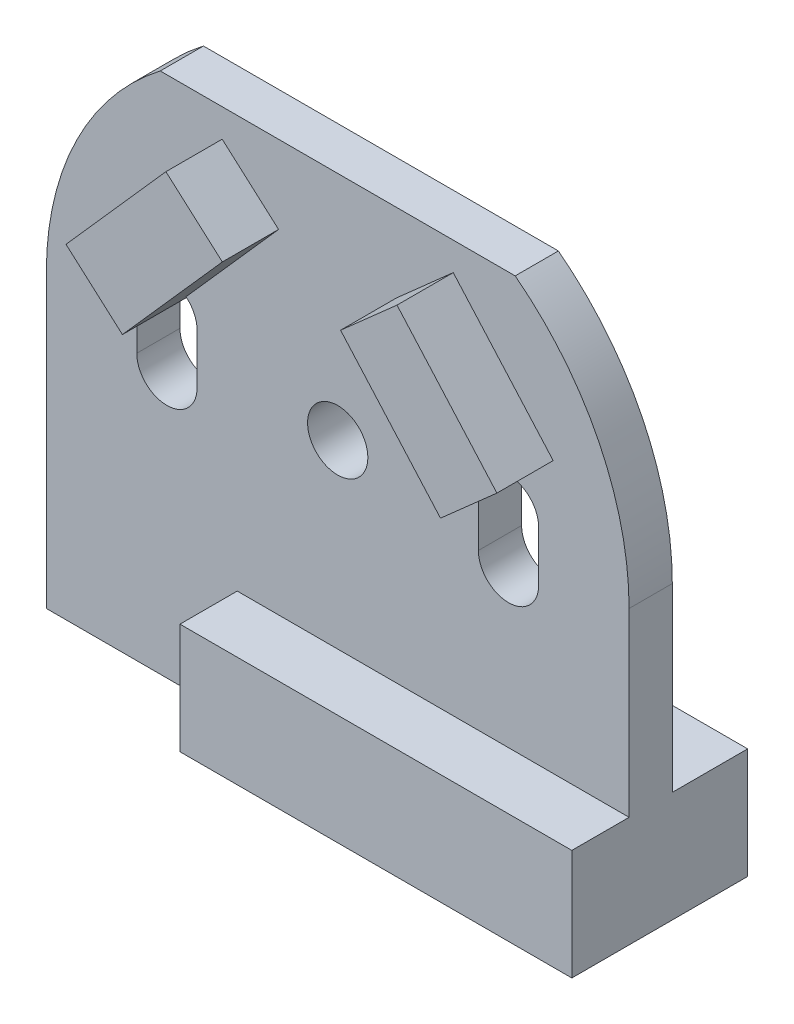
SolidWorks part; units mm, degrees
ref_plane "Front Plane" through (0, 0, 0) normal (0, 0, 1) x (1, 0, 0)
ref_plane "Top Plane" through (0, 0, 0) normal (0, 1, 0) x (1, 0, 0)
ref_plane "Right Plane" through (0, 0, 0) normal (1, 0, 0) x (0, 0, -1)
sketch "Sketch1" plane through (0, 0, 0) normal (0, 0, 1) x (1, 0, 0)
  line L0 (-3.4, 0.5) -> (-3.4, -0.5) construction
  line L1 (-5.8, -5.8) -> (5.8, -5.8)
  line L2 (-5.8, -5.8) -> (-5.8, 4.6)
  line L3 (-5.8, 4.6) -> (5.8, 4.6)
  line L4 (5.8, -5.8) -> (5.8, 4.6)
  line L5 (-2.8, 0.5) -> (-2.8, -0.5)
  line L6 (-4, 0.5) -> (-4, -0.5)
  line L7 (3.4, 0.5) -> (3.4, -0.5) construction
  line L8 (4, 0.5) -> (4, -0.5)
  line L9 (2.8, 0.5) -> (2.8, -0.5)
  line L10 (-2.3, 4.0398) -> (-4.2887, 1.7937)
  line L11 (-4.2887, 1.7937) -> (-3.1656, 0.7993)
  line L12 (-3.1656, 0.7993) -> (-1.1769, 3.0455)
  line L13 (-1.1769, 3.0455) -> (-2.3, 4.0398)
  line L14 (1.1769, 3.0455) -> (2.3, 4.0398)
  line L15 (2.3, 4.0398) -> (4.2887, 1.7937)
  line L16 (4.2887, 1.7937) -> (3.1656, 0.7993)
  line L17 (3.1656, 0.7993) -> (1.1769, 3.0455)
  line L18 (0, 0) -> (-2.1713, 1.9224) construction
  line L19 (0, 0) -> (2.1713, 1.9224) construction
  line L20 (0, 0) -> (0, 5.8) construction
  line L22 (5.8, -5.8) -> (-2, -5.8)
  line L23 (5.8, -5.8) -> (5.8, -3.6)
  line L24 (5.8, -3.6) -> (-2, -3.6)
  line L25 (-2, -5.8) -> (-2, -3.6)
  circle A0 centre (0, 0) radius 5.8
  circle A1 centre (0, 0) radius 0.6
  arc A2 (-2.8, 0.5) -> (-4, 0.5) centre (-3.4, 0.5) ccw
  arc A3 (-4, -0.5) -> (-2.8, -0.5) centre (-3.4, -0.5) ccw
  arc A4 (4, 0.5) -> (2.8, 0.5) centre (3.4, 0.5) ccw
  arc A5 (2.8, -0.5) -> (4, -0.5) centre (3.4, -0.5) ccw
  point P10 (-3.4, 0)
  point P15 (3.4, 0)
  dimension "D1" = 11.6
  dimension "D3" = 1.2
  dimension "D6" = 0.6
  dimension "D2" = 4.6
  dimension "D4" = 2.4
  dimension "D5" = 2.4
  dimension "D7" = 1
  dimension "D8" = 2.3
  dimension "D9" = 2.3
  dimension "D10" = 1.5
  dimension "D11" = 3
  dimension "D12" = 2.9
  dimension "D13" = 7.8
  dimension "D14" = 2.2
extrude "Boss-Extrude1" add sketch "Sketch1" along normal blind 0.86 contours L3 A0 L25 L24 A5 L9 A4 L17 L14 L15 L16 L8 A3 L6 A2 L11 L10 L13 L12 L5 A1 | A0 L2 L1 L25 | L25 A0 L24 | A0 L25 L1 | A0 L22 L4 L24 | A0 L24 L4 | A4 L16 L15 L14 L17 | A2 L12 L13 L10 L11 region at (-4.6051, -4.4646, 0) region at (-1.5031, -5.6939, 0) region at (-5.0648, 2.4964, 0) region at (4.275, -4.9456, 0) region at (0.7374, -4.5515, 0) region at (5.4324, -2.7206, 0) region at (-2.7253, 2.4411, 0) region at (2.7253, 2.4411, 0)
extrude "Boss-Extrude2" add sketch "Sketch1<3>" along normal blind 1.98 contours A2 L11 L12 L13 L10 | A4 L16 L15 L14 L17 | L11 A2 | L16 A4 region at (-2.7253, 2.4411, 0) region at (-3.234, 0.9777, 0) region at (2.7253, 2.4411, 0) region at (3.234, 0.9777, 0)
sketch "Sketch1<3>" plane through (0, 0, 0) normal (0, 0, 1) x (1, 0, 0) same geometry as "Sketch1"
extrude "Boss-Extrude3" add sketch "Sketch1<4>" against normal blind 1.5 and the other way blind 2 contours L25 A0 L24 | A0 L22 L4 L24 | A0 L25 L1 region at (-1.5031, -5.6939, 0) region at (4.275, -4.9456, 0) region at (0.7374, -4.5515, 0)
sketch "Sketch1<4>" plane through (0, 0, 0) normal (0, 0, 1) x (1, 0, 0) same geometry as "Sketch1"
